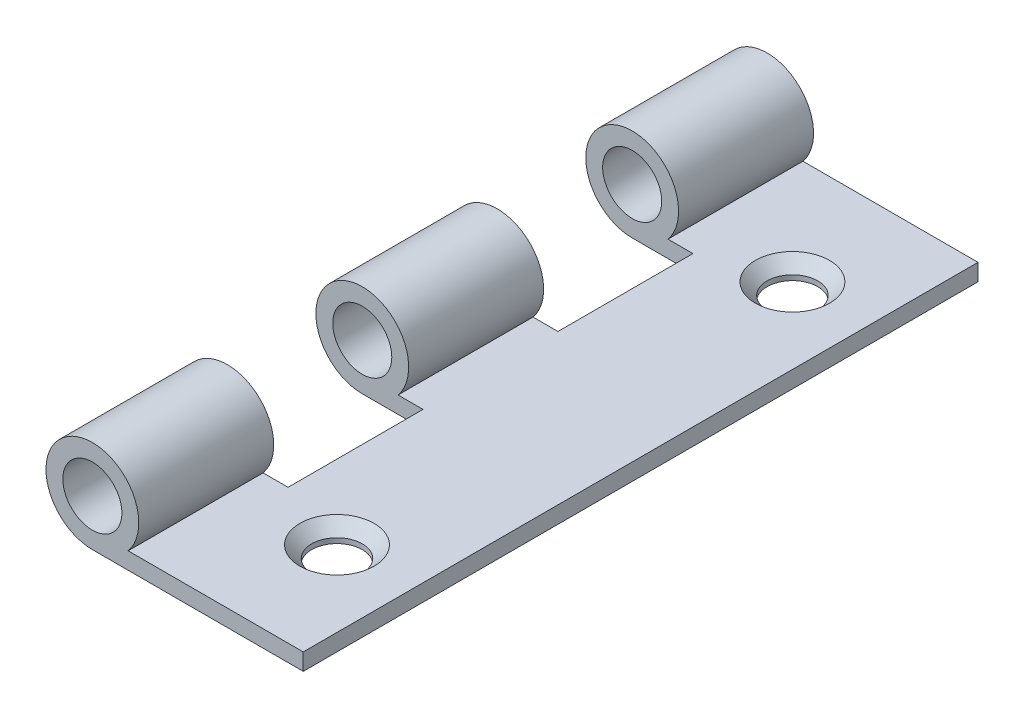
SolidWorks part; units mm, degrees
ref_plane "Plan de face" through (0, 0, 0) normal (0, 0, 1) x (1, 0, 0)
ref_plane "Plan de dessus" through (0, 0, 0) normal (0, 1, 0) x (1, 0, 0)
ref_plane "Plan de droite" through (0, 0, 0) normal (1, 0, 0) x (0, 0, -1)
sketch "Esquisse1" plane through (0, 0, 0) normal (0, 0, 1) x (1, 0, 0)
  line L0 (12.5, -1.75) -> (2.1213, -1.75)
  line L1 (12.5, -1.75) -> (12.5, -2.75)
  line L2 (12.5, -2.75) -> (0, -2.75)
  circle A0 centre (0, 0) radius 1.75
  arc A2 (2.1213, -1.75) -> (0, -2.75) centre (0, 0) ccw
  dimension "D2" = 2.75
  dimension "D1" = 1
  dimension "D3" = 12.5
extrude "Boss.-Extru.1" add sketch "Esquisse1" along normal blind 40
sketch "Esquisse2" plane through (0, -1.75, 0) normal (0, 1, 0) x (1, 0, 0)
  line L1 (-14.2, -8) -> (3.6, -8)
  line L2 (-14.2, -8) -> (-14.2, -16)
  line L3 (-14.2, -16) -> (3.6, -16)
  line L4 (3.6, -8) -> (3.6, -16)
  line L5 (-14.2, -24) -> (3.6, -24)
  line L6 (-14.2, -24) -> (-14.2, -32)
  line L7 (-14.2, -32) -> (3.6, -32)
  line L8 (3.6, -24) -> (3.6, -32)
  line L10 (12.5, 0) -> (2.1213, 0) construction
  line L11 (12.5, -40) -> (12.5, 0) construction
  dimension "D1" = 8
  dimension "D2" = 8
  dimension "D3" = 8
  dimension "D4" = 8.9
  dimension "D5" = 8
extrude "Enlèv. mat.-Extru.3" cut sketch "Esquisse2" against normal blind 20 and the other way blind 20
hole_wizard "Dégagement M31" positions "Esquisse4" profile "Esquisse3" hole size "M3" standard "Ansi Metric"
sketch "Esquisse4" plane through (0, -1.75, 0) normal (0, 1, 0) x (1, 0, 0)
  line L0 (12.5, -40) -> (12.5, 0) construction
  line L1 (12.5, -40) -> (2.1213, -40) construction
  line L2 (12.5, 0) -> (2.1213, 0) construction
  point P0 (8, -33.5)
  point P2 (8, -6.5)
  dimension "D1" = 4.5
  dimension "D2" = 4.5
  dimension "D3" = 6.5
  dimension "D4" = 6.5
sketch "Esquisse3" plane through (8, -1.75, 33.5) normal (1, 0, 0) x (0, 0, 1)
  line L0 (0, 0) -> (0, 10.9013)
  line L1 (0, 10.9013) -> (1.5, 10)
  line L2 (1.5, 10) -> (1.5, 0.7)
  line L3 (1.5, 0.7) -> (2.2, 0)
  line L5 (2.2, 0) -> (0, 0)
  line L6 (-1.5, 0.7) -> (-2.2, 0) construction
  line L10 (0, 10.9013) -> (-1.5, 10) construction
  line L11 (0, -6.35) -> (0, 107.95) construction
  dimension "Diamètre du perçage" = 3
  dimension "Profondeur du perçage" = 10
  dimension "Diamètre du fraisage entrant" = 4.4
  dimension "Angle du fraisage entrant" = 90
  dimension "Angle de pointe" = 118
